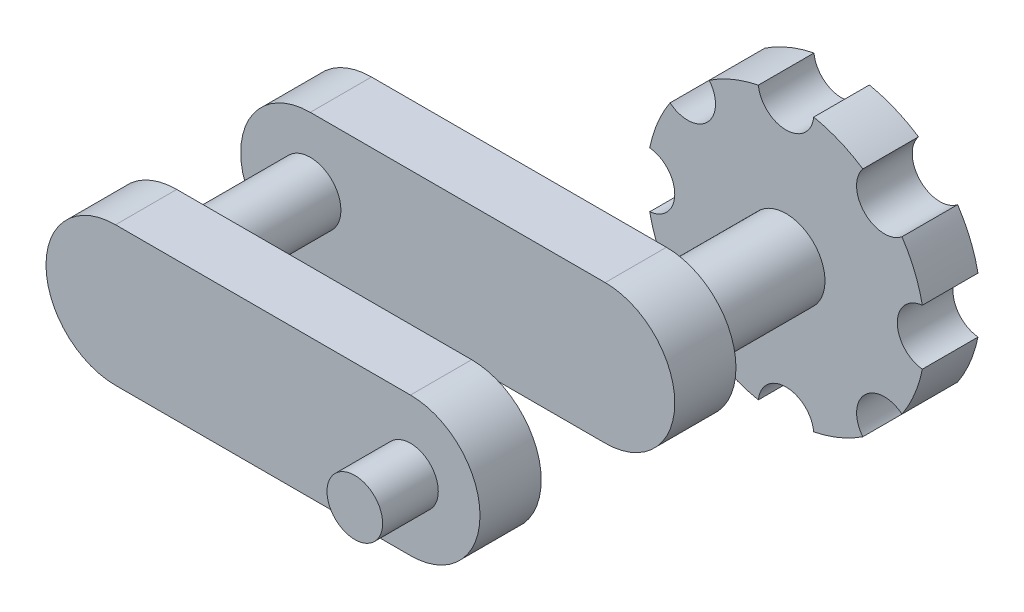
SolidWorks part; units mm, degrees
ref_plane "Front Plane" through (0, 0, 0) normal (0, 0, 1) x (1, 0, 0)
ref_plane "Top Plane" through (0, 0, 0) normal (0, 1, 0) x (1, 0, 0)
ref_plane "Right Plane" through (0, 0, 0) normal (1, 0, 0) x (0, 0, -1)
sketch "Sketch1" plane through (0, 0, 0) normal (0, 0, 1) x (1, 0, 0)
  circle A0 centre (0, 0) radius 5
  dimension "D1" = 10
extrude "Boss-Extrude1" add sketch "Sketch1" against normal blind 2
sketch "Sketch2" plane through (0, 0, 0) normal (0, 0, 1) x (1, 0, 0)
  circle A0 centre (0, 0) radius 1.4
  dimension "D1" = 2.8
extrude "Boss-Extrude2" add sketch "Sketch2" along normal blind 4.3 contours A0
sketch "Sketch3" plane through (0, 0, 4.3) normal (0, 0, 1) x (1, 0, 0)
  line L0 (0, 0) -> (-10.6, 0) construction
  line L1 (0, -2.5) -> (-10.6, -2.5)
  line L2 (0, 2.5) -> (-10.6, 2.5)
  arc A0 (0, -2.5) -> (0, 2.5) centre (0, 0) ccw
  arc A1 (-10.6, 2.5) -> (-10.6, -2.5) centre (-10.6, 0) ccw
  point P3 (-5.3, 0)
  dimension "D2" = 2.5
  dimension "D1" = 10.6
extrude "Boss-Extrude3" add sketch "Sketch3" along normal blind 2.2
sketch "Sketch4" plane through (0, 0, 6.5) normal (0, 0, 1) x (1, 0, 0)
  circle A1 centre (-10.6, 0) radius 1.1
  dimension "D1" = 2.2
extrude "Boss-Extrude4" add sketch "Sketch4" along normal blind 4.8
sketch "Sketch7" plane through (0, 0, 11.3) normal (0, 0, 1) x (1, 0, 0)
  line L0 (-10.6, 0) -> (0, 0) construction
  line L3 (-10.6, 2.5) -> (0, 2.5)
  line L4 (-10.6, -2.5) -> (0, -2.5)
  arc A2 (-10.6, 2.5) -> (-10.6, -2.5) centre (-10.6, 0) ccw
  arc A3 (0, -2.5) -> (0, 2.5) centre (0, 0) ccw
  point P4 (-5.3, 0)
  dimension "D2" = 2.5
  dimension "D1" = 10.6
extrude "Boss-Extrude7" add sketch "Sketch7" along normal blind 2.2
sketch "Sketch8" plane through (0, 0, 13.5) normal (0, 0, 1) x (1, 0, 0)
  circle A0 centre (0, 0) radius 1
  dimension "D1" = 2
extrude "Boss-Extrude8" add sketch "Sketch8" along normal blind 2
sketch "Sketch9" plane through (0, 0, -2) normal (0, 0, -1) x (-1, 0, 0)
  circle A0 centre (5, 0) radius 1
  circle A1 centre (0, 0) radius 5 construction
  dimension "D1" = 2
extrude "Cut-Extrude1" cut sketch "Sketch9" against normal up to next
pattern_circular "CirPattern1" count 8 over 360 about axis through (0, 0, -2) along (0, 0, 1) of "Cut-Extrude1"
sketch "Sketch10" plane through (0, 0, -2) normal (0, 0, -1) x (-1, 0, 0)
  circle A0 centre (0, 0) radius 2
  dimension "D1" = 4
extrude "Cut-Extrude3" cut sketch "Sketch10" against normal blind 1 contours A0
fillet "Fillet6" radius 0.5 2 edges at (-2, 0, -2) (-2, 0, -1)
